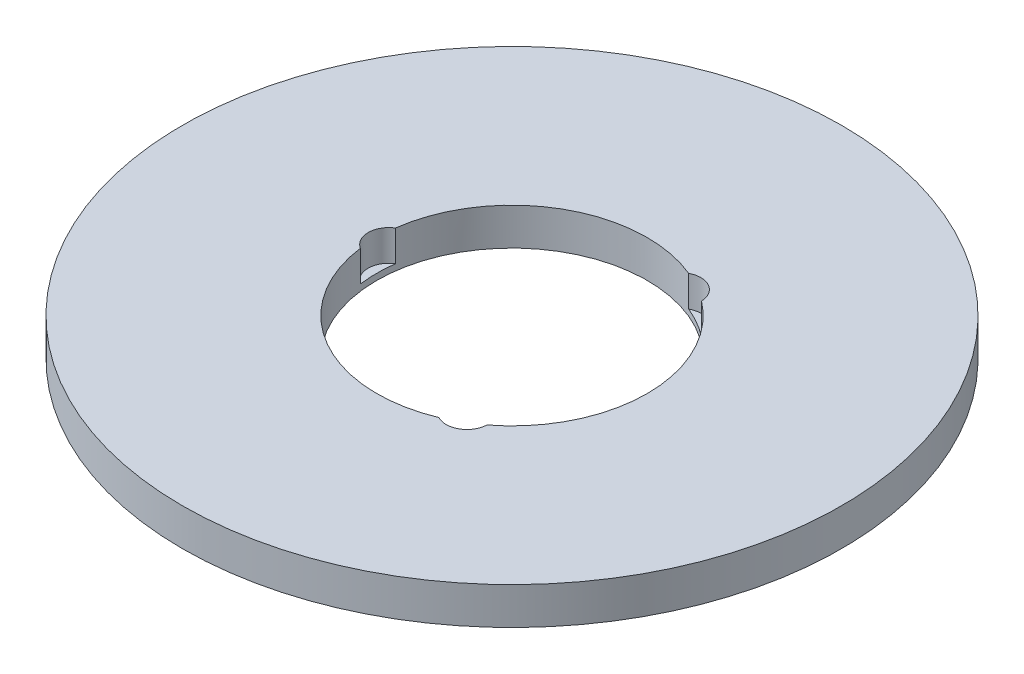
SolidWorks part; units mm, degrees
ref_plane "Front Plane" through (0, 0, 0) normal (0, 0, 1) x (1, 0, 0)
ref_plane "Top Plane" through (0, 0, 0) normal (0, 1, 0) x (1, 0, 0)
ref_plane "Right Plane" through (0, 0, 0) normal (1, 0, 0) x (0, 0, -1)
sketch "Sketch1" plane through (0, 0, 0) normal (0, 1, 0) x (1, 0, 0)
  circle A0 centre (0, 0) radius 97.5
  dimension "FLANGE_OD" = 195
extrude "Boss-Extrude1" add sketch "Sketch1" along normal blind 11
sketch "Sketch2" plane through (0, 0, 0) normal (0, 1, 0) x (1, 0, 0)
  circle A0 centre (0, 0) radius 40
  dimension "BORE_D" = 80
extrude "Cut-Extrude1" cut sketch "Sketch2" along normal through all
sketch "Sketch3" plane through (0, 11, 0) normal (0, 1, 0) x (1, 0, 0)
  circle A0 centre (0, 0) radius 36.4335 construction
  circle A1 centre (-36.4335, 0) radius 6.1114
  dimension "BOLT_D" = 12.2228
  dimension "BOLT_PCD" = 72.8669
extrude "Cut-Extrude2" cut sketch "Sketch3" against normal blind 9.1468
pattern_circular "CirPattern1" count 3 over 360 about axis through (0, 0, 0) along (0, 1, 0) of "Cut-Extrude2"
